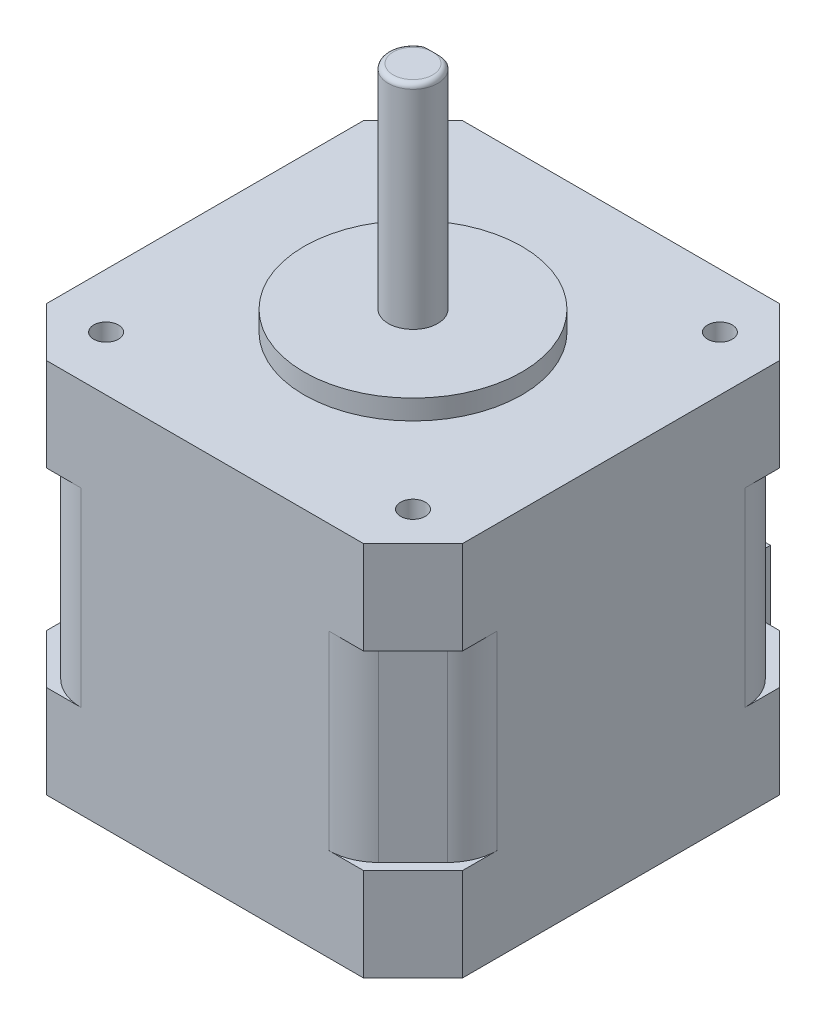
SolidWorks part; units mm, degrees
ref_plane "Front Plane" through (0, 0, 0) normal (0, 0, 1) x (1, 0, 0)
ref_plane "Top Plane" through (0, 0, 0) normal (0, 1, 0) x (1, 0, 0)
ref_plane "Right Plane" through (0, 0, 0) normal (1, 0, 0) x (0, 0, -1)
sketch "Sketch1" plane through (0, 0, 0) normal (0, 1, 0) x (1, 0, 0)
  line L1 (21, 21) -> (-21, 21)
  line L2 (21, 21) -> (21, -21)
  line L3 (21, -21) -> (-21, -21)
  line L4 (-21, 21) -> (-21, -21)
  line L5 (21, 21) -> (-21, -21) construction
  line L6 (21, -21) -> (-21, 21) construction
  point P0 (0, 0)
  dimension "D1" = 42
  dimension "D2" = 42
extrude "Boss-Extrude1" add sketch "Sketch1" along normal blind 38
sketch "Sketch2" plane through (0, 38, 0) normal (0, 1, 0) x (1, 0, 0)
  circle A0 centre (0, 0) radius 11
  dimension "D1" = 22
extrude "Boss-Extrude2" add sketch "Sketch2" along normal blind 2
sketch "Sketch3" plane through (0, 40, 0) normal (0, 1, 0) x (1, 0, 0)
  circle A0 centre (0, 0) radius 2.5
  dimension "D1" = 5
extrude "Boss-Extrude3" add sketch "Sketch3" along normal blind 3.5
sketch "Sketch4" plane through (0, 43.5, 0) normal (0, 1, 0) x (1, 0, 0)
  line L0 (0, -2.5) -> (0, 2) construction
  line L1 (1.5, 2) -> (-1.5, 2)
  circle A0 centre (0, 0) radius 2.5 construction
  circle A1 centre (0, 0) radius 2.5 construction
  arc A2 (-1.5, 2) -> (1.5, 2) centre (0, 0) ccw
  point P11 (0, 2)
  circle M2 centre (0, 0) radius 2.5
  dimension "D1" = 4.5
extrude "Boss-Extrude4" add sketch "Sketch4" along normal blind 18 contours L0 L1 M2 | L0 A2 L1
hole_wizard "M3 Tapped Hole1" positions "Sketch8" profile "Sketch10" tap size "M3" standard "ISO"
sketch "Sketch8" plane through (0, 38, 0) normal (0, 1, 0) x (1, 0, 0)
  line L0 (0, -21) -> (0, 21) construction
  line L1 (-21, -21) -> (21, -21) construction
  line L2 (21, 21) -> (-21, 21) construction
  line L4 (21, 0) -> (-21, 0) construction
  line L5 (21, -21) -> (21, 21) construction
  line L6 (-21, 21) -> (-21, -21) construction
  point P0 (-15.5, 15.5)
  point P17 (15.5, 15.5)
  point P19 (15.5, -15.5)
  point P21 (-15.5, -15.5)
  dimension "D1" = 15.5
  dimension "D2" = 15.5
  dimension "D3" = 15.5
  dimension "D4" = 15.5
  dimension "D5" = 15.5
  dimension "D6" = 15.5
  dimension "D7" = 15.5
  dimension "D8" = 15.5
sketch "Sketch10" plane through (-15.5, 38, -15.5) normal (1, 0, 0) x (0, 0, 1)
  line L0 (0, 0) -> (0, 5.7511)
  line L1 (0, 5.7511) -> (1.25, 5)
  line L2 (1.25, 5) -> (1.25, 0)
  line L5 (1.25, 0) -> (0, 0)
  line L10 (0, 5.7511) -> (-1.25, 5) construction
  line L11 (0, -6.35) -> (0, 107.95) construction
  dimension "Tap Drill Dia." = 2.5
  dimension "Tap Drill Depth" = 5
  dimension "Drill Angle" = 118
cosmetic thread "Hole Thread1" parameters "D1"=2.4, "D2"=3
cosmetic thread "Hole Thread2" parameters "D1"=2.4, "D2"=3
cosmetic thread "Hole Thread3" parameters "D1"=2.4, "D2"=3
cosmetic thread "Hole Thread4" parameters "D1"=2.4, "D2"=3
chamfer "Chamfer1" distance 5 angle 45 4 edges at (-21, 19, -21) (-21, 19, 21) (21, 19, 21) (21, 19, -21)
sketch "Sketch11" plane through (18.5, 0, 18.5) normal (0.7071, 0, 0.7071) x (0.7071, 0, -0.7071)
  line L8 (-3.5355, 38) -> (3.5355, 38) construction
  line L9 (5, 9.4) -> (-5, 9.4)
  line L10 (5, 9.4) -> (5, 28.6)
  line L11 (5, 28.6) -> (-5, 28.6)
  line L12 (-5, 9.4) -> (-5, 28.6)
  line L13 (5, 9.4) -> (-5, 28.6) construction
  line L14 (5, 28.6) -> (-5, 9.4) construction
  point P0 (0, 19)
  dimension "D1" = 9.4
  dimension "D2" = 19.2
  dimension "D3" = 10
  dimension "D4" = 5
extrude "Cut-Extrude2" cut sketch "Sketch11" against normal blind 1
sketch "Sketch12" plane through (-18.5, 0, 18.5) normal (-0.7071, 0, 0.7071) x (0.7071, 0, 0.7071)
  line L0 (-3.5355, 38) -> (3.5355, 38) construction
  line L1 (5, 28.6) -> (-5, 28.6)
  line L2 (5, 28.6) -> (5, 9.4)
  line L3 (5, 9.4) -> (-5, 9.4)
  line L4 (-5, 28.6) -> (-5, 9.4)
  line L5 (5, 28.6) -> (-5, 9.4) construction
  line L6 (5, 9.4) -> (-5, 28.6) construction
  point P0 (0, 19)
  dimension "D1" = 10
  dimension "D2" = 19.2
  dimension "D3" = 9.4
  dimension "D4" = 5
extrude "Cut-Extrude3" cut sketch "Sketch12" against normal blind 1
sketch "Sketch13" plane through (-18.5, 0, -18.5) normal (-0.7071, 0, -0.7071) x (-0.7071, 0, 0.7071)
  line L0 (-3.5355, 38) -> (3.5355, 38) construction
  line L1 (5, 28.6) -> (-5, 28.6)
  line L2 (5, 28.6) -> (5, 9.4)
  line L3 (5, 9.4) -> (-5, 9.4)
  line L4 (-5, 28.6) -> (-5, 9.4)
  line L5 (5, 28.6) -> (-5, 9.4) construction
  line L6 (5, 9.4) -> (-5, 28.6) construction
  point P0 (0, 19)
  dimension "D1" = 10
  dimension "D2" = 19.2
  dimension "D3" = 9.4
  dimension "D4" = 5
extrude "Cut-Extrude4" cut sketch "Sketch13" against normal blind 1
sketch "Sketch14" plane through (18.5, 0, -18.5) normal (0.7071, 0, -0.7071) x (-0.7071, 0, -0.7071)
  line L0 (-3.5355, 38) -> (3.5355, 38) construction
  line L1 (5, 28.6) -> (-5, 28.6)
  line L2 (5, 28.6) -> (5, 9.4)
  line L3 (5, 9.4) -> (-5, 9.4)
  line L4 (-5, 28.6) -> (-5, 9.4)
  line L5 (5, 28.6) -> (-5, 9.4) construction
  line L6 (5, 9.4) -> (-5, 28.6) construction
  point P0 (0, 19)
  dimension "D1" = 10
  dimension "D2" = 5
  dimension "D3" = 19.2
  dimension "D4" = 9.4
extrude "Cut-Extrude5" cut sketch "Sketch14" against normal blind 1
fillet "Fillet1" radius 5 8 edges at (21, 19, -14.5858) (14.5858, 19, -21) (-14.5858, 19, -21) (-21, 19, -14.5858) (-21, 19, 14.5858) (-14.5858, 19, 21) (14.5858, 19, 21) (21, 19, 14.5858)
sketch "Sketch15" plane through (0, 0, -21) normal (0, 0, -1) x (-1, 0, 0)
  line L0 (-16, 0) -> (16, 0) construction
  line L1 (-8.1, 0) -> (8.1, 0)
  line L2 (-8.1, 0) -> (-8.1, 9.4)
  line L3 (-8.1, 9.4) -> (8.1, 9.4)
  line L4 (8.1, 0) -> (8.1, 9.4)
  dimension "D1" = 16.2
  dimension "D2" = 8.1
  dimension "D3" = 9.4
extrude "Boss-Extrude5" add sketch "Sketch15" along normal blind 7
fillet "Fillet3" radius 0.5 2 edges at (0, 61.5, 2.5) (0, 61.5, -2)
